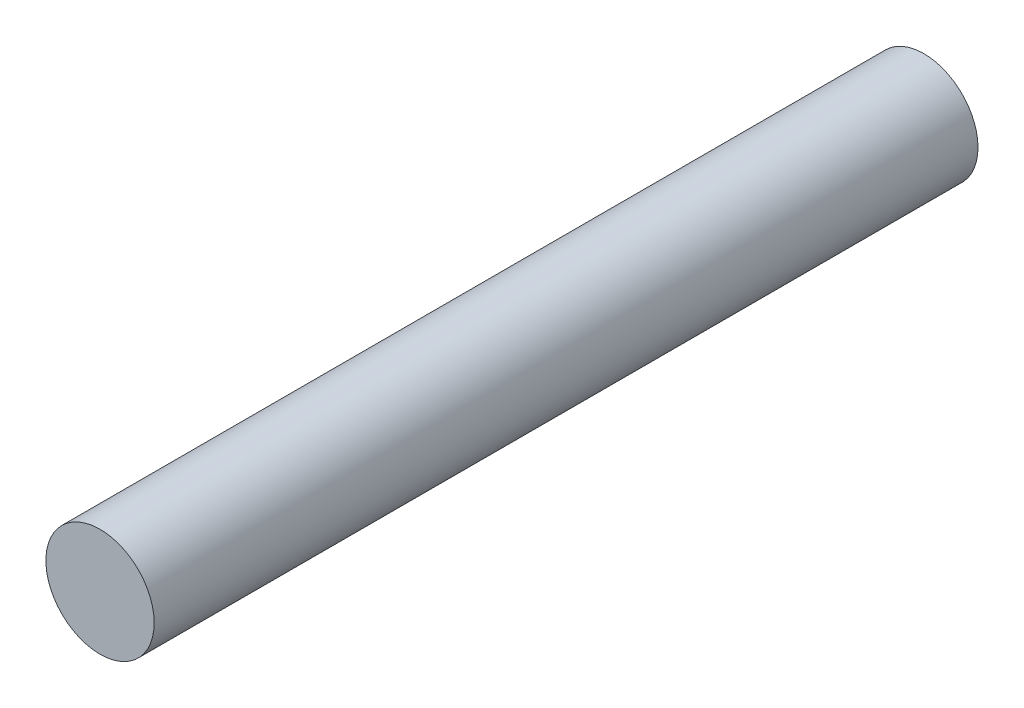
SolidWorks part; units mm, degrees
material "Magnetorquers"
ref_plane "Piano frontale" through (0, 0, 0) normal (0, 0, 1) x (1, 0, 0)
ref_plane "Piano superiore" through (0, 0, 0) normal (0, 1, 0) x (1, 0, 0)
ref_plane "Piano destro" through (0, 0, 0) normal (1, 0, 0) x (0, 0, -1)
sketch "Schizzo1" plane through (0, 0, 0) normal (0, 0, 1) x (1, 0, 0)
  circle A0 centre (0, 0) radius 25
  dimension "D1" = 50
extrude "Estrusione-Estrusione1" add sketch "Schizzo1" along normal blind 190.25 and the other way blind 190.25
